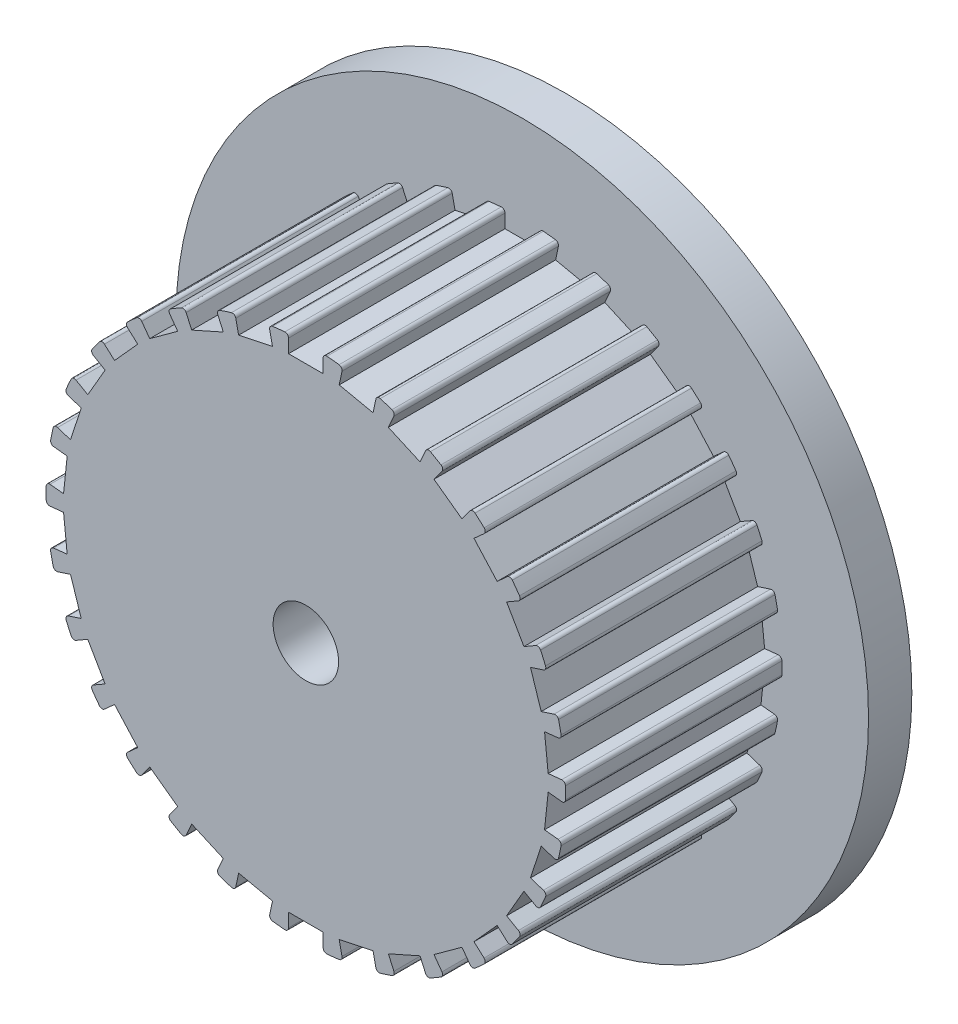
SolidWorks part; units mm, degrees
ref_plane "Front Plane" through (0, 0, 0) normal (0, 0, 1) x (1, 0, 0)
ref_plane "Top Plane" through (0, 0, 0) normal (0, 1, 0) x (1, 0, 0)
ref_plane "Right Plane" through (0, 0, 0) normal (1, 0, 0) x (0, 0, -1)
sketch "Sketch1" plane through (0, 0, 0) normal (0, 0, 1) x (1, 0, 0)
  circle A0 centre (0, 0) radius 12.7
  dimension "D1" = 25.4
extrude "Boss-Extrude1" add sketch "Sketch1" along normal blind 1.5875
sketch "Sketch2" plane through (0, 0, 1.5875) normal (0, 0, 1) x (1, 0, 0)
  circle A0 centre (0, 0) radius 9.525
  dimension "D1" = 19.05
extrude "Boss-Extrude2" add sketch "Sketch2" along normal blind 7.9375
sketch "Sketch3" plane through (0, 0, 9.525) normal (0, 0, 1) x (1, 0, 0)
  circle A0 centre (0, 0) radius 1.2
  dimension "D1" = 2.4
extrude "Cut-Extrude1" cut sketch "Sketch3" against normal through all
sketch "Sketch4" plane through (0, 0, 9.525) normal (0, 0, 1) x (1, 0, 0)
  line L0 (0, 8.8688) -> (0, 9.525) construction
  line L6 (-0.635, 9.5038) -> (0.635, 9.5038)
  line L7 (-0.635, 9.5038) -> (-0.635, 10.1388)
  line L8 (-0.635, 10.1388) -> (0.635, 10.1388)
  line L9 (0.635, 9.5038) -> (0.635, 10.1388)
  line L10 (-0.635, 9.5038) -> (0.635, 9.5038)
  line L11 (-0.635, 9.5038) -> (-0.635, 8.8688)
  line L12 (-0.635, 8.8688) -> (0.635, 8.8688)
  line L13 (0.635, 9.5038) -> (0.635, 8.8688)
  circle A0 centre (0, 0) radius 9.525 construction
  circle A5 centre (0, 0) radius 9.525 construction
  point P13 (0, 9.4966)
  dimension "D1" = 1.27
  dimension "D2" = 0.635
  dimension "D4" = 0.635
extrude "Cut-Extrude2" cut sketch "Sketch4" against normal up to surface (7.9375 mm away) contours L12 L13 L10 L11 | L7 L6 L9 L8 up to face at (9.525, 0, 1.5875)
fillet "Fillet2" radius 0.127 2 edges at (0.635, 9.5038, 5.5563) (-0.635, 9.5038, 5.5563)
pattern_circular "CirPattern1" count 30 over 360 about axis through (0, 0, 1.5875) along (0, 0, 1) of "Cut-Extrude2", "Fillet2"
